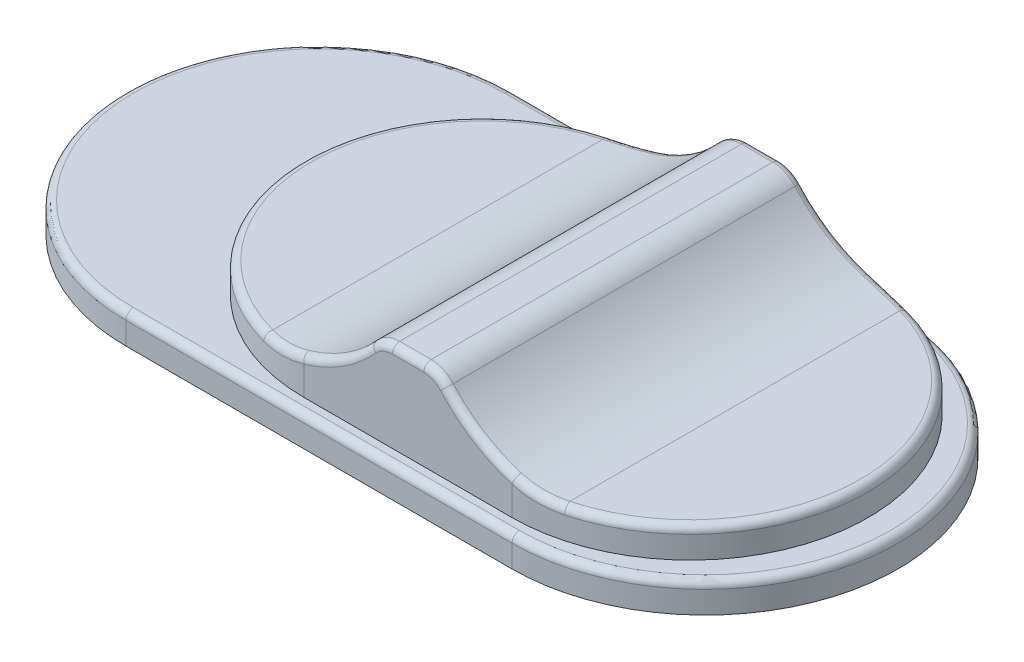
SolidWorks part; units mm, degrees
ref_plane "Front Plane" through (0, 0, 0) normal (0, 0, 1) x (1, 0, 0)
ref_plane "Top Plane" through (0, 0, 0) normal (0, 1, 0) x (1, 0, 0)
ref_plane "Right Plane" through (0, 0, 0) normal (1, 0, 0) x (0, 0, -1)
sketch "Sketch1" plane through (0, 0, 0) normal (0, 1, 0) x (1, 0, 0)
  line L0 (-6.5, 0) -> (6.5, 0) construction
  line L1 (-6.5, 6.5) -> (6.5, 6.5)
  line L2 (-6.5, -6.5) -> (6.5, -6.5)
  arc A0 (-6.5, 6.5) -> (-6.5, -6.5) centre (-6.5, 0) ccw
  arc A1 (6.5, -6.5) -> (6.5, 6.5) centre (6.5, 0) ccw
  point P3 (0, 0)
  dimension "D1" = 13
  dimension "D2" = 13
extrude "Boss-Extrude1" add sketch "Sketch1" along normal blind 1
sketch "Sketch2" plane through (0, 0, 0) normal (0, 0, 1) x (1, 0, 0)
  line L0 (-7, 1) -> (-7, 2)
  line L1 (-6.5, 1) -> (-13, 1) construction
  line L2 (-7, 2) -> (1.5, 2)
  line L3 (1.5, 2) -> (1.5, 4)
  line L4 (1.5, 4) -> (3.5, 4)
  line L5 (3.5, 4) -> (3.5, 2)
  line L6 (3.5, 2) -> (12, 2)
  line L7 (12, 2) -> (12, 1)
  line L8 (13, 0) -> (13, 1) construction
  line L9 (-7, 1) -> (12, 1)
  dimension "D1" = 2
  dimension "D2" = 8.5
  dimension "D3" = 1
  dimension "D4" = 2
  dimension "D5" = 1
extrude "Boss-Extrude2" add sketch "Sketch2" along normal offset from surface 0.5 and the other way offset from surface (6 mm away) 0.5 up to face at (0, 0.5, 6.5) other way up to face at (0, 0.5, -6.5)
sketch "Sketch3" plane through (0, 2, 0) normal (0, 1, 0) x (1, 0, 0)
  line L0 (-1, 6) -> (-7, 6)
  line L1 (-7, 6) -> (-7, -6)
  line L2 (-7, -6) -> (-1, -6)
  line L3 (6, 6) -> (12, 6)
  line L4 (12, 6) -> (12, -6)
  line L5 (9, 6) -> (-7, 6) construction
  line L6 (9, -6) -> (-7, -6) construction
  line L7 (3.5, 6) -> (12, 6) construction
  line L8 (3.5, -6) -> (12, -6) construction
  line L9 (12, -3.4641) -> (12, 3.4641) construction
  line L10 (-7, -6) -> (-7, 6) construction
  line L11 (12, -6) -> (6, -6)
  arc A0 (-1, 6) -> (-1, -6) centre (-1, 0) ccw
  arc A1 (6, 6) -> (6, -6) centre (6, 0) cw
extrude "Cut-Extrude1" cut sketch "Sketch3" against normal up to surface (1 mm away)
fillet "Fillet1" radius 5 2 edges at (3.5, 2, 0) (1.5, 2, 0)
fillet "Fillet2" radius 1 2 edges at (3.5, 4, 0) (1.5, 4, 0)
fillet "Fillet3" radius 0.25 20 edges at (0.2103, 2.7983, -6) (1.5639, 3.9129, -6) (2.5, 4, -6) (3.4361, 3.9129, -6) (4.7897, 2.7983, -6) (4.7897, 2.7983, 6) (3.4361, 3.9129, 6) (2.5, 4, 6) (1.5639, 3.9129, 6) (0.2103, 2.7983, 6) (0, 1, -6.5) (13, 1, 0) (0, 1, 6.5) (12, 2, 0) (-13, 1, 0) (-7, 2, 0)
